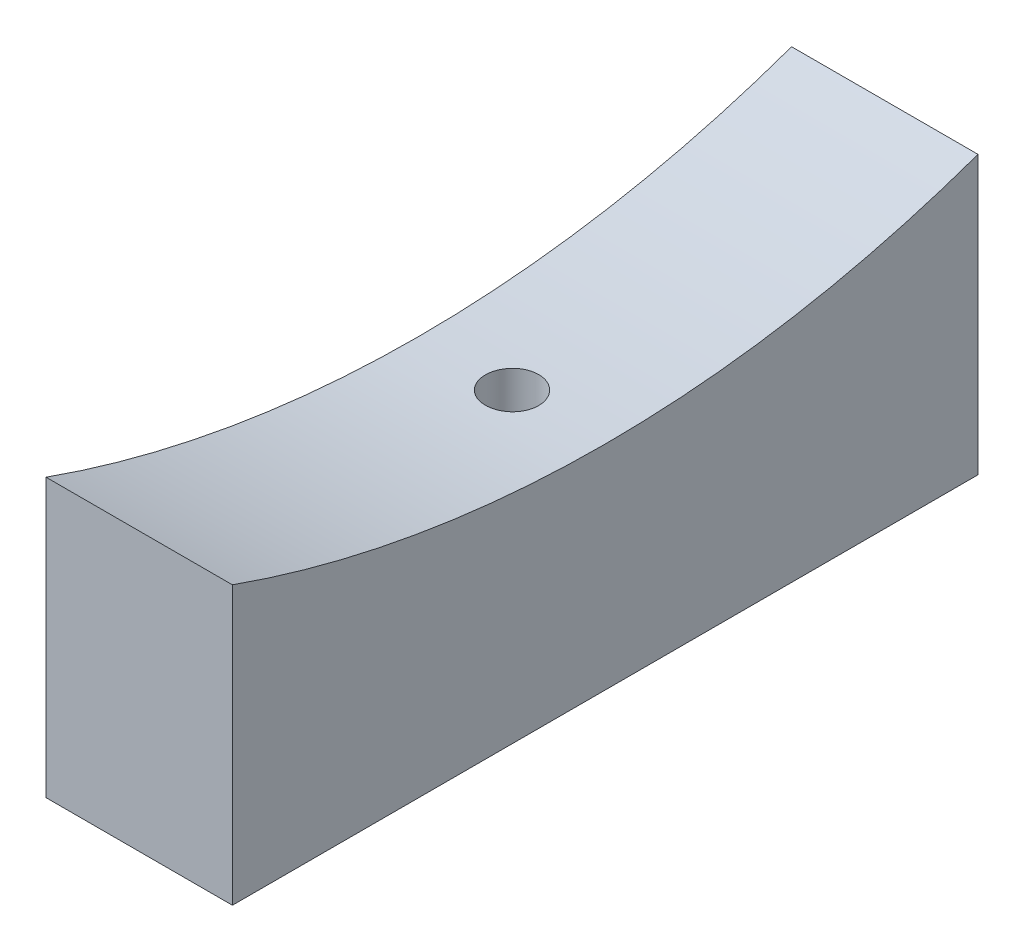
SolidWorks part; units mm, degrees
ref_plane "Plan de face" through (0, 0, 0) normal (0, 0, 1) x (1, 0, 0)
ref_plane "Plan de dessus" through (0, 0, 0) normal (0, 1, 0) x (1, 0, 0)
ref_plane "Plan de droite" through (0, 0, 0) normal (1, 0, 0) x (0, 0, -1)
sketch "Esquisse1" plane through (0, 0, 0) normal (1, 0, 0) x (0, 0, -1)
  line L0 (-42, -117.7327) -> (-42, -149)
  line L1 (-42, -149) -> (42, -149)
  line L2 (42, -149) -> (42, -117.7327)
  line L5 (0, -149) -> (0, -125) construction
  line L7 (-42, -138.7944) -> (34.0021, -138.7944) construction
  line L8 (34.0021, -138.7944) -> (42, -138.7944) construction
  arc A0 (-42, -117.7327) -> (42, -117.7327) centre (0, 0) ccw
  dimension "D2" = 125
  dimension "D1" = 24
  dimension "D3" = 84
extrude "Boss.-Extru.1" add sketch "Esquisse1" along normal blind 21
sketch "Esquisse2" plane through (0, -149, 0) normal (0, -1, 0) x (1, 0, 0)
  line L0 (10.5, 42) -> (10.5, 0) construction
  line L1 (21, 42) -> (0, 42) construction
  line L2 (10.5, 0) -> (10.5, -42) construction
  line L3 (21, -42) -> (0, -42) construction
  circle A0 centre (10.5, 0) radius 3
  dimension "D1" = 6
extrude "Enlèv. mat.-Extru.1" cut sketch "Esquisse2" against normal up to next
